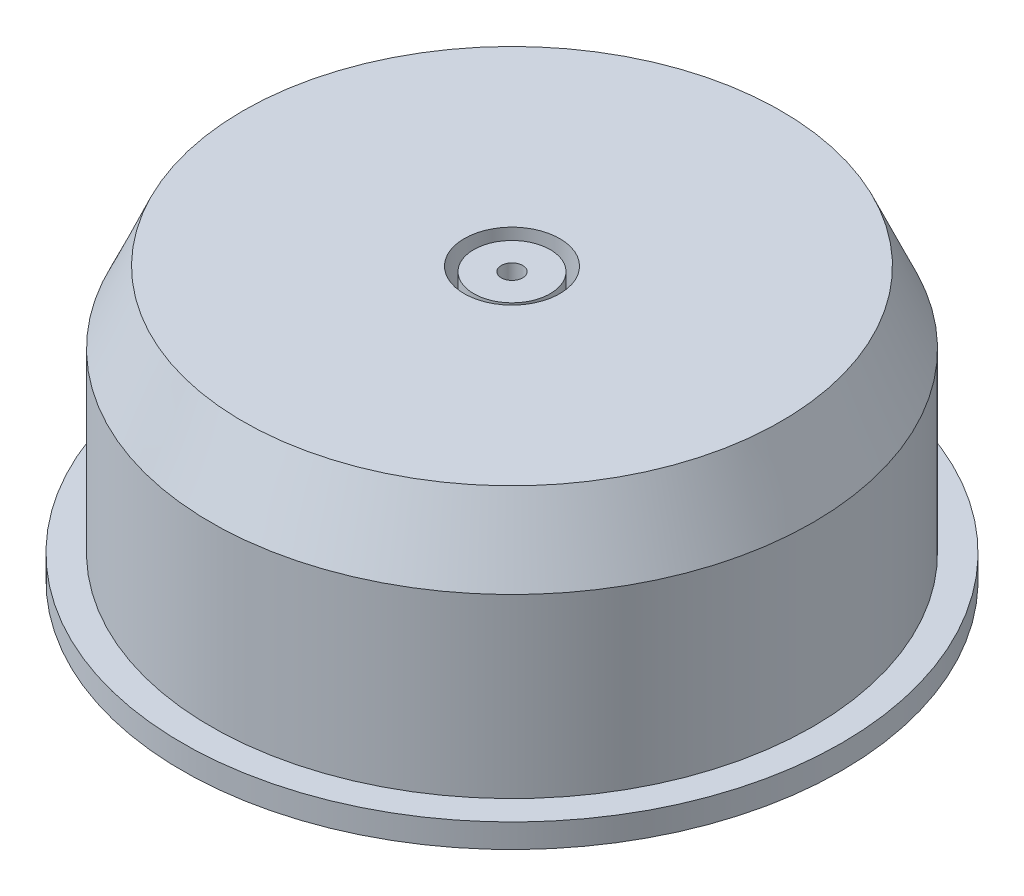
SolidWorks part; units mm, degrees
material "Д16Т ГОСТ 4784-97"
ref_plane "Спереди" through (0, 0, 0) normal (0, 0, 1) x (1, 0, 0)
ref_plane "Сверху" through (0, 0, 0) normal (0, 1, 0) x (1, 0, 0)
ref_plane "Справа" through (0, 0, 0) normal (1, 0, 0) x (0, 0, -1)
other "Configuration Table"
sketch "Эскиз2" plane through (0, 0, 0) normal (0, 0, 1) x (1, 0, 0)
  line L0 (-10, -1.9782) -> (-56.3333, -1.9782)
  line L1 (-56.3333, -1.9782) -> (-63, -16.9782)
  line L5 (-63, -16.9782) -> (-63, -53.9782)
  line L6 (-63, -53.9782) -> (-69, -53.9782)
  line L7 (-69, -53.9782) -> (-69, -58.9782)
  line L8 (-69, -58.9782) -> (-34.2989, -58.9782)
  line L9 (-34.2989, -58.9782) -> (-25.2989, -62.9782)
  line L10 (-25.2989, -62.9782) -> (0, -62.9782)
  line L11 (0, -2.9782) -> (0, -70.5392) construction
  line L12 (0, -2.9782) -> (0, -62.9782)
  line L13 (-8, -13.7306) -> (-8, -2.9782)
  line L14 (0, -2.9782) -> (-8, -2.9782)
  line L15 (-8, -13.7306) -> (-10, -13.7306)
  line L16 (-10, -13.7306) -> (-10, -1.9782)
  dimension "D2" = 63
  dimension "D3" = 15
  dimension "D6" = 37
  dimension "D7" = 5
  dimension "D9" = 4
  dimension "D11" = 6
  dimension "D12" = 8
  dimension "60" = 60
revolve "Повернуть1" add sketch "Эскиз2" angle 360 about L11
sketch "Эскиз3" plane through (0, -62.9782, 0) normal (0, -1, 0) x (1, 0, 0)
  circle A0 centre (0, 0) radius 8
extrude "Бобышка-Вытянуть1" add sketch "Эскиз3" along normal blind 27
sketch "Эскиз4" plane through (0, -89.9782, 0) normal (0, -1, 0) x (1, 0, 0)
  line L1 (-11.0002, 11.8096) -> (10.8692, 11.8096)
  line L2 (-11.0002, 11.8096) -> (-11.0002, 5)
  line L3 (-11.0002, 5) -> (10.8692, 5)
  line L4 (10.8692, 11.8096) -> (10.8692, 5)
  dimension "D1" = 5
extrude "Вырез-Вытянуть1" cut sketch "Эскиз4" against normal blind 46
sketch "Эскиз5" plane through (0, -89.9782, 0) normal (0, -1, 0) x (1, 0, 0)
  circle A0 centre (0, 0) radius 3.5
  dimension "D1" = 7
extrude "Вырез-Вытянуть2" cut sketch "Эскиз5" against normal blind 70
hole_wizard "Зенковка для винта с полупотайной головкой M51" positions "Эскиз6" profile "Эскиз7" countersink size "M5" standard "ISO"
sketch "Эскиз6" plane through (0, -58.9782, 0) normal (0, -1, 0) x (-1, 0, 0)
  point P0 (1.1577, 60)
  dimension "D1" = 60
sketch "Эскиз7" plane through (-1.1577, -58.9782, -60) normal (1, 0, 0) x (0, 0, -1)
  line L0 (0, 0) -> (0, 15.6524)
  line L1 (0, 15.6524) -> (2.75, 14)
  line L2 (2.75, 14) -> (2.75, 2.45)
  line L3 (2.75, 2.45) -> (5.2, 0)
  line L5 (5.2, 0) -> (0, 0)
  line L6 (-2.75, 2.45) -> (-5.2, 0) construction
  line L10 (0, 15.6524) -> (-2.75, 14) construction
  line L11 (0, -6.35) -> (0, 107.95) construction
  dimension "Диаметр отверстия" = 5.5
  dimension "Глубина отверстия" = 14
  dimension "Диаметр передней зенковки" = 10.4
  dimension "Угол передней зенковки" = 90
  dimension "Угол заточки сверла" = 118
pattern_circular "Круговой массив1" count 6 over 360 about axis through (0, -58.9782, 0) along (0, 1, 0) of "Зенковка для винта с полупотайной головкой M51"
sketch "Эскиз8" plane through (0, -1.9782, 0) normal (0, 1, 0) x (1, 0, 0)
  circle A0 centre (0, 0) radius 6
  dimension "D1" = 12
extrude "Вырез-Вытянуть3" [suppressed] cut sketch "Эскиз8" against normal blind 6
sketch "Эскиз9" [suppressed] plane through (0, -6, 0) normal (0, 1, 0) x (1, 0, 0)
  circle A0 centre (0, 0) radius 2.5
  dimension "D1" = 5
extrude "Бобышка-Вытянуть2" [suppressed] add sketch "Эскиз9" along normal blind 12
sketch "Эскиз10" [suppressed] plane through (0, 6, 0) normal (0, 1, 0) x (1, 0, 0)
  circle A0 centre (0, 0) radius 4.5
  dimension "D1" = 9
extrude "Бобышка-Вытянуть3" [suppressed] add sketch "Эскиз10" along normal blind 5
sketch "Эскиз11" [suppressed] plane through (0, 11, 0) normal (0, 1, 0) x (1, 0, 0)
  circle A0 centre (0, 0) radius 2.65
  dimension "D1" = 5.3
extrude "Вырез-Вытянуть4" [suppressed] cut sketch "Эскиз11" against normal blind 3 contours A0
chamfer "Фаска1" [suppressed] distance 1 angle 45
hole_wizard "Отверстие с зазором M41" positions "Эскиз13" profile "Эскиз12" hole size "M4" standard "ISO"
sketch "Эскиз13" plane through (0, -2.9782, 0) normal (0, 1, 0) x (1, 0, 0)
  point P0 (0, 0)
sketch "Эскиз12" plane through (0, -2.9782, 0) normal (1, 0, 0) x (0, 0, 1)
  line L0 (0, 0) -> (0, 15.3519)
  line L1 (0, 15.3519) -> (2.25, 14)
  line L2 (2.25, 14) -> (2.25, 0)
  line L5 (2.25, 0) -> (0, 0)
  line L10 (0, 15.3519) -> (-2.25, 14) construction
  line L11 (0, -6.35) -> (0, 107.95) construction
  dimension "Диаметр отверстия" = 4.5
  dimension "Глубина отверстия" = 14
  dimension "Угол заточки сверла" = 118
sketch "Эскиз14" plane through (0, -62.9782, 0) normal (0, -1, 0) x (1, 0, 0)
  circle A0 centre (0, 0) radius 8
  circle A1 centre (0, 0) radius 9.9506
extrude "Вырез-Вытянуть5" cut sketch "Эскиз14" against normal blind 10
